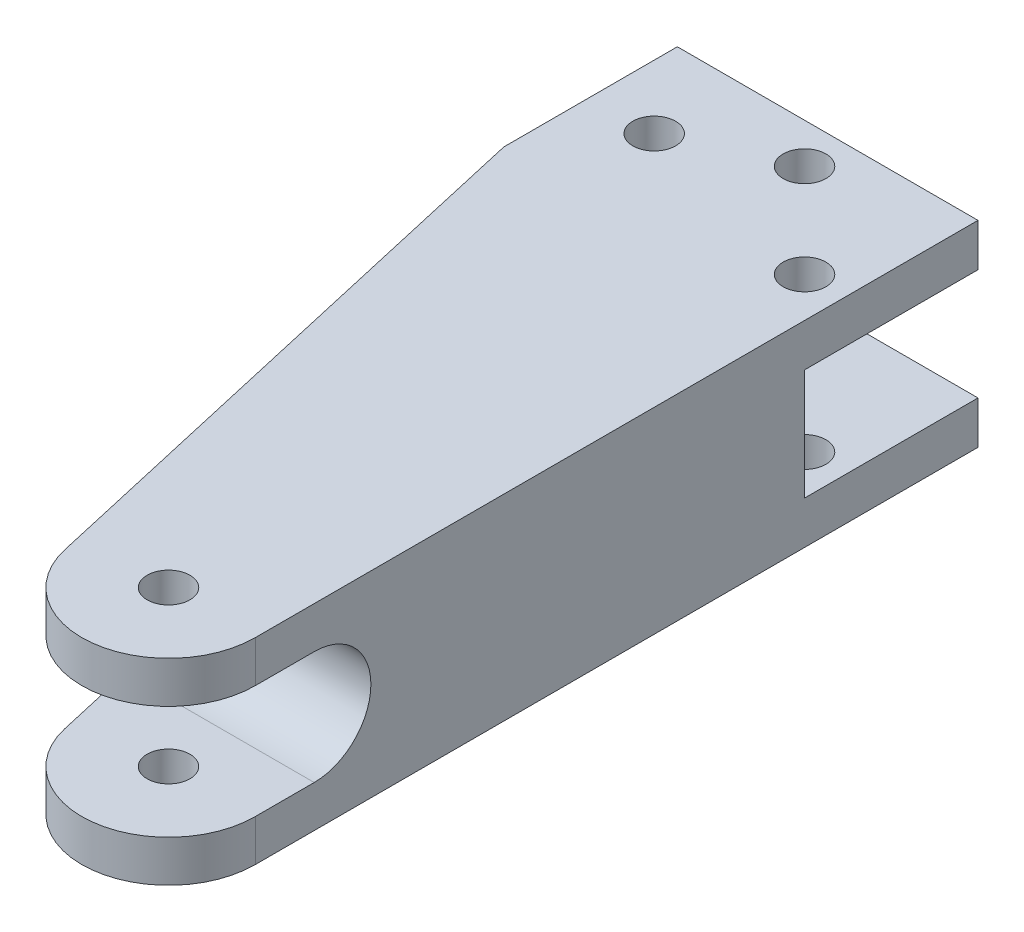
SolidWorks part; units mm, degrees
material "2024-T3"
ref_plane "Front Plane" through (0, 0, 0) normal (0, 0, 1) x (1, 0, 0)
ref_plane "Top Plane" through (0, 0, 0) normal (0, 1, 0) x (1, 0, 0)
ref_plane "Right Plane" through (0, 0, 0) normal (1, 0, 0) x (0, 0, -1)
sketch "Sketch1" plane through (0, 0, 0) normal (0, 0, 1) x (1, 0, 0)
  line L0 (-9.525, -10.795) -> (9.525, -10.795)
  line L1 (-9.525, -10.795) -> (-9.525, 10.795)
  line L2 (9.525, -10.795) -> (9.525, 10.795)
  line L3 (-9.525, 10.795) -> (9.525, 10.795)
  line L4 (-9.525, -10.795) -> (9.525, 10.795) construction
  line L5 (9.525, -10.795) -> (-9.525, 10.795) construction
  point P1 (0, 0)
  dimension "D1" = 21.59
  dimension "D2" = 19.05
extrude "Boss-Extrude1" add sketch "Sketch1" along normal blind 88.9
sketch "Sketch3" plane through (0, 10.795, 0) normal (0, 1, 0) x (1, 0, 0)
  line L0 (-9.525, -88.9) -> (-9.525, 0) construction
  line L1 (9.525, -88.9) -> (9.525, 0) construction
  line L2 (9.525, -88.9) -> (-9.525, -88.9) construction
  arc A0 (-9.525, -79.375) -> (9.525, -79.375) centre (0, -79.375) ccw
extrude "Cut-Extrude-Thin1" cut sketch "Sketch3" against normal blind 88.9 and the other way through all thin thin type one direction wall 25.4
sketch "Sketch4" plane through (0, 10.795, 0) normal (0, 1, 0) x (1, 0, 0)
  line L0 (5.1435, -14.6685) -> (9.525, -14.6685) construction
  line L1 (9.525, -79.375) -> (9.525, 0) construction
  line L2 (-9.525, 0) -> (9.525, -19.05) construction
  line L3 (-5.1435, -4.3815) -> (-5.1435, 0) construction
  line L4 (-9.525, 0) -> (9.525, 0) construction
  line L5 (-9.525, 0) -> (-9.525, -19.05) construction
  line L6 (-9.525, -19.05) -> (9.525, -19.05) construction
  line L7 (9.525, 0) -> (9.525, -19.05) construction
  circle A0 centre (0, -79.375) radius 2.3495
  circle A1 centre (5.1435, -14.6685) radius 2.3495
  circle A2 centre (-5.1435, -4.3815) radius 2.3495
  dimension "D1" = 4.699
  dimension "D2" = 4.3815
  dimension "D3" = 4.3815
extrude "Cut-Extrude1" cut sketch "Sketch4" against normal through all
sketch "Sketch5" plane through (0, 10.795, 0) normal (0, 1, 0) x (1, 0, 0)
  line L0 (-9.525, 0) -> (-23.495, 0)
  line L1 (-23.495, 0) -> (-23.495, -19.05)
  line L2 (-9.525, -79.375) -> (-9.525, 0) construction
  line L3 (-9.525, -79.375) -> (-9.525, 0)
  line L4 (-23.495, -19.05) -> (-9.2876, -81.4883)
  arc A0 (-9.525, -79.375) -> (9.525, -79.375) centre (0, -79.375) ccw construction
  arc A1 (-9.525, -79.375) -> (9.525, -79.375) centre (0, -79.375) ccw
  circle A2 centre (-16.51, -9.525) radius 2.3495
  circle A3 centre (-5.1435, -4.3815) radius 2.3495 construction
  point P14 (-16.51, 0)
  point P17 (-23.495, -9.525)
  line M9 (-9.525, 0) -> (-9.525, -79.375)
  arc M10 (-9.525, -79.375) -> (9.525, -79.375) centre (0, -79.375) ccw
  dimension "D1" = 13.97
  dimension "D2" = 19.05
  dimension "D3" = 12.819
extrude "Boss-Extrude2" add sketch "Sketch5" against normal up to surface (21.59 mm away) contours L1 L4 L0 A2 M10 M9 region at (-15.0361, 10.795, 28.5077) up to face at (0, -10.795, 81.7245)
sketch "Sketch6" plane through (9.525, 0, 0) normal (1, 0, 0) x (0, 0, -1)
  line L0 (19.05, -6.096) -> (19.05, 6.096)
  line L1 (19.05, -6.096) -> (-19.05, -6.096)
  line L2 (19.05, 6.096) -> (-19.05, 6.096)
  line L3 (-19.05, -6.096) -> (-19.05, 6.096)
  line L4 (19.05, -6.096) -> (-19.05, 6.096) construction
  line L5 (19.05, 6.096) -> (-19.05, -6.096) construction
  line L6 (-92.075, -6.223) -> (-72.898, -6.223)
  line L7 (-92.075, -6.223) -> (-92.075, 6.223)
  line L9 (-92.075, 6.223) -> (-72.898, 6.223)
  line L10 (-92.075, -6.223) -> (-69.1843, 4.9934) construction
  line L11 (-69.1843, -4.9934) -> (-92.075, 6.223) construction
  line L12 (-79.375, -10.795) -> (-79.375, 10.795) construction
  line L13 (-79.375, -10.795) -> (-79.375, 10.795) construction
  arc A0 (-72.898, 6.223) -> (-72.898, -6.223) centre (-72.898, 0) cw
  point P1 (0, 0)
  point P2 (-79.375, 0)
  point P14 (-79.375, 0)
  dimension "D1" = 12.192
  dimension "D2" = 19.05
extrude "Cut-Extrude2" cut sketch "Sketch6" against normal through all
move or copy body "Body-Move/Copy1" [suppressed] bodies to move or copy 105
